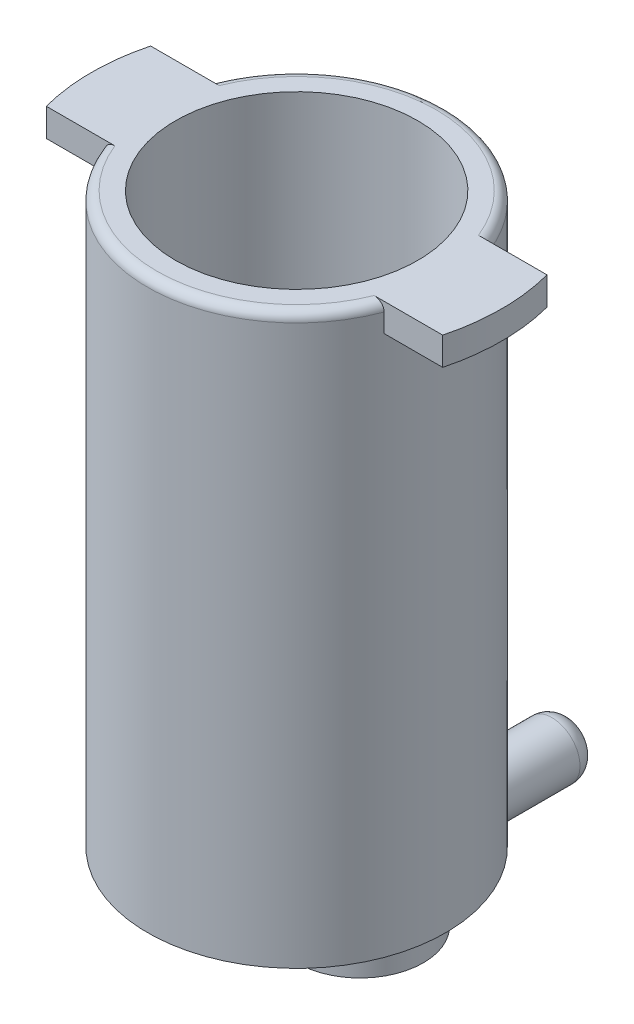
SolidWorks part; units mm, degrees
ref_plane "Front Plane" through (0, 0, 0) normal (0, 0, 1) x (1, 0, 0)
ref_plane "Top Plane" through (0, 0, 0) normal (0, 1, 0) x (1, 0, 0)
ref_plane "Right Plane" through (0, 0, 0) normal (1, 0, 0) x (0, 0, -1)
sketch "Sketch1" plane through (0, 0, 0) normal (0, 1, 0) x (1, 0, 0)
  circle A0 centre (0, 0) radius 8
extrude "Boss-Extrude1" add sketch "Sketch1" along normal blind 30.5
shell "Shell1" thickness 1.5 removed face at (0, 30.5, 8)
sketch "Sketch2" plane through (0, 0, 0) normal (0, -1, 0) x (1, 0, 0)
  circle A0 centre (0, -3.4) radius 3.4
extrude "Boss-Extrude2" add sketch "Sketch2" along normal blind 5.4 contours A0
shell "Shell2" thickness 1.5 removed face at (0, 1.5, 6.5)
sketch "Sketch4" plane through (0, 0, 0) normal (0, -1, 0) x (1, 0, 0)
  line L0 (-3.4, -3.4) -> (3.4, -3.4) construction
  circle A0 centre (0, -3.4) radius 3.4 construction
  circle A1 centre (0, -3.4) radius 3.4 construction
ref_plane "Plane1" through (0, 0, -3.4) normal (0, 0, 1) x (1, 0, 0)
sketch "Sketch5" plane through (0, 0, -3.4) normal (0, 0, 1) x (1, 0, 0)
  line L0 (0, 0) -> (0, -5.4) construction
  line L1 (-3.4, -5.4) -> (3.4, -5.4) construction
  circle A0 centre (0, -2.3538) radius 2.45
extrude "Boss-Extrude5" add sketch "Sketch5" against normal blind 4.9
sketch "Sketch6" plane through (0, 0, -8.3) normal (0, 0, -1) x (-1, 0, 0)
  circle A0 centre (0, -2.3538) radius 1.5
extrude "Boss-Extrude6" add sketch "Sketch6" along normal blind 6.3
sketch "Sketch7" plane through (0, 0, -14.6) normal (0, 0, -1) x (-1, 0, 0)
  circle A0 centre (0, -2.3538) radius 0.95
extrude "Cut-Extrude1" cut sketch "Sketch7" against normal blind 11.3
sketch "Sketch8" plane through (0, -3.9, 0) normal (0, 1, 0) x (1, 0, 0)
  line L0 (-3.4, 3.4) -> (3.4, 3.4) construction
  circle A0 centre (0, 3.4) radius 1.9
extrude "Cut-Extrude2" cut sketch "Sketch8" along normal through all contours A0
fillet "Fillet1" radius 1 1 edges at (-1.5, -2.3538, -14.6)
fillet "Fillet2" radius 0.5 1 edges at (0, 30.5, 8)
sketch "Sketch9" plane through (0, 30.5, 0) normal (0, 1, 0) x (1, 0, 0)
  line L0 (0, 1.3156) -> (0, -1.546) construction
  line L3 (-10.6377, 2.8) -> (-5.866, 2.8)
  line L4 (-10.6377, -2.8) -> (-5.866, -2.8)
  arc A1 (-5.866, 2.8) -> (-5.866, -2.8) centre (0, 0) ccw
  arc A2 (-10.6377, 2.8) -> (-10.6377, -2.8) centre (0, 0) ccw
  circle A3 centre (0, 0) radius 6.5 construction
  circle A4 centre (0, 0) radius 6.5 construction
extrude "Boss-Extrude7" add sketch "Sketch9" against normal blind 1.5
mirror "Mirror1" about plane through (0, 0, 0) normal (1, 0, 0) of bodies 107
